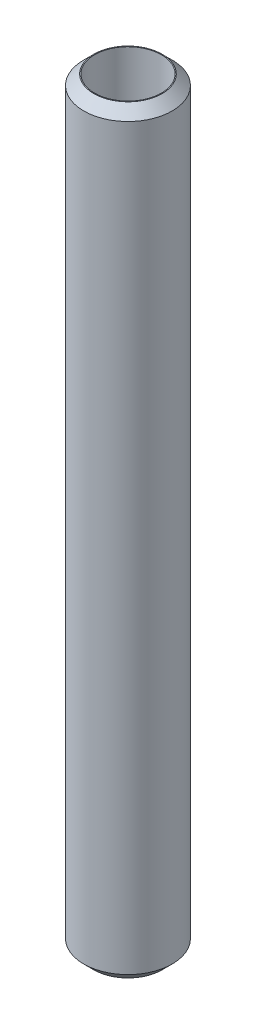
SolidWorks part; units mm, degrees
ref_plane "Front Plane" through (0, 0, 0) normal (0, 0, 1) x (1, 0, 0)
ref_plane "Top Plane" through (0, 0, 0) normal (0, 1, 0) x (1, 0, 0)
ref_plane "Right Plane" through (0, 0, 0) normal (1, 0, 0) x (0, 0, -1)
sketch "Sketch1" plane through (0, 0, 0) normal (0, 1, 0) x (1, 0, 0)
  circle A0 centre (0, 0) radius 25
  dimension "SHAFT_OD" = 50
extrude "Boss-Extrude1" add sketch "Sketch1" along normal blind 429.2791
sketch "Sketch2" plane through (0, 0, 0) normal (0, 1, 0) x (1, 0, 0)
  circle A0 centre (0, 0) radius 18.8569
  dimension "BORE_D" = 37.7139
extrude "Cut-Extrude1" cut sketch "Sketch2" along normal through all
chamfer "Chamfer1" distance 5.6549 angle 45 2 edges at (0, 429.2791, 25) (0, 0, 25)
